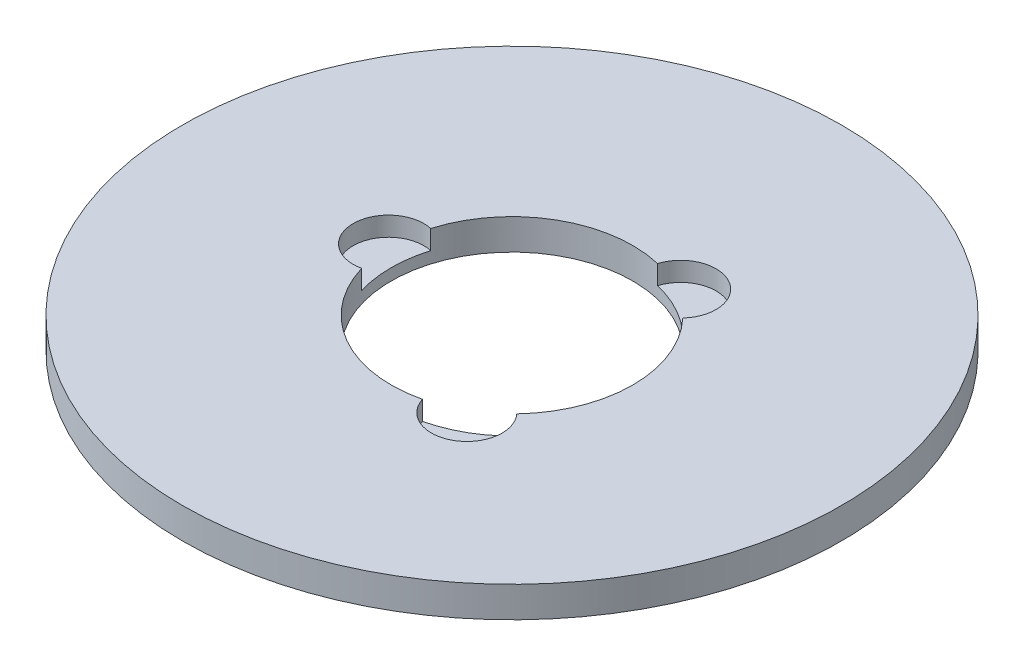
SolidWorks part; units mm, degrees
ref_plane "Front Plane" through (0, 0, 0) normal (0, 0, 1) x (1, 0, 0)
ref_plane "Top Plane" through (0, 0, 0) normal (0, 1, 0) x (1, 0, 0)
ref_plane "Right Plane" through (0, 0, 0) normal (1, 0, 0) x (0, 0, -1)
sketch "Sketch1" plane through (0, 0, 0) normal (0, 1, 0) x (1, 0, 0)
  circle A0 centre (0, 0) radius 75
  dimension "FLANGE_OD" = 150
extrude "Boss-Extrude1" add sketch "Sketch1" along normal blind 7
sketch "Sketch2" plane through (0, 0, 0) normal (0, 1, 0) x (1, 0, 0)
  circle A0 centre (0, 0) radius 27.5
  dimension "BORE_D" = 55
extrude "Cut-Extrude1" cut sketch "Sketch2" along normal through all
sketch "Sketch3" plane through (0, 7, 0) normal (0, 1, 0) x (1, 0, 0)
  circle A0 centre (0, 0) radius 28.1022 construction
  circle A1 centre (-28.1022, 0) radius 8.0501
  dimension "BOLT_D" = 16.1002
  dimension "BOLT_PCD" = 56.2045
extrude "Cut-Extrude2" cut sketch "Sketch3" against normal blind 4.3657
pattern_circular "CirPattern1" count 3 over 360 about axis through (0, 0, 0) along (0, 1, 0) of "Cut-Extrude2"
